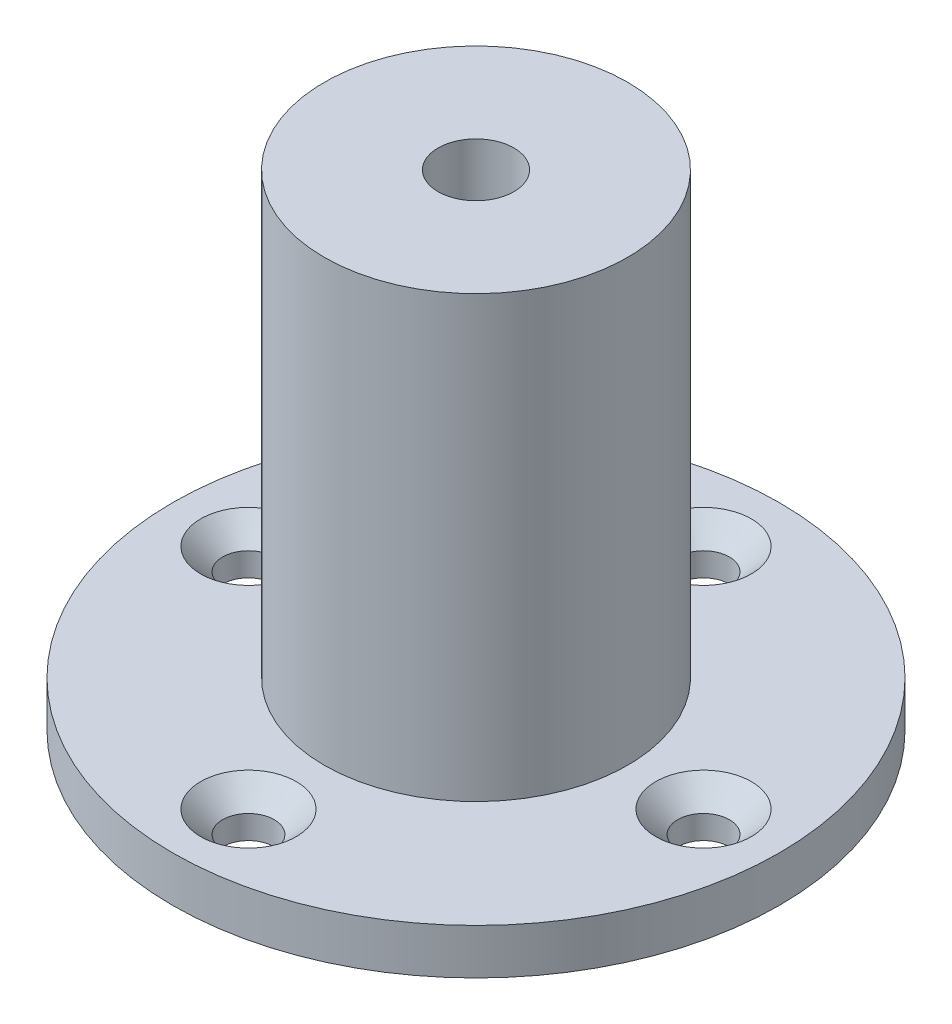
SolidWorks part; units mm, degrees
ref_plane "Front Plane" through (0, 0, 0) normal (0, 0, 1) x (1, 0, 0)
ref_plane "Top Plane" through (0, 0, 0) normal (0, 1, 0) x (1, 0, 0)
ref_plane "Right Plane" through (0, 0, 0) normal (1, 0, 0) x (0, 0, -1)
sketch "Sketch1" plane through (0, 0, 0) normal (0, 1, 0) x (1, 0, 0)
  circle A0 centre (0, 0) radius 10
  dimension "D1" = 20
extrude "Boss-Extrude1" add sketch "Sketch1" along normal blind 32 contours A0
sketch "Sketch2" plane through (0, 0, 0) normal (0, -1, 0) x (1, 0, 0)
  circle A0 centre (0, 0) radius 20
  dimension "D1" = 40
extrude "Boss-Extrude2" add sketch "Sketch2" against normal blind 3
hole_wizard "CSK for M3 Countersunk Flat Head Screw1" positions "Sketch4" profile "Sketch3" countersink size "M3" standard "ISO" end condition through all
sketch "Sketch4" plane through (0, 3, 0) normal (0, 1, 0) x (1, 0, 0)
  point P0 (0, 15)
  dimension "D1" = 15
sketch "Sketch3" plane through (0, 3, -15) normal (1, 0, 0) x (0, 0, 1)
  line L0 (0, 0) -> (0, 3)
  line L1 (0, 3) -> (1.7, 3)
  line L2 (1.7, 3) -> (1.7, 1.45)
  line L3 (1.7, 1.45) -> (3.15, 0)
  line L5 (3.15, 0) -> (0, 0)
  line L6 (-1.7, 1.45) -> (-3.15, 0) construction
  line L11 (0, -6.35) -> (0, 107.95) construction
  dimension "Thru Hole Dia." = 3.4
  dimension "Thru Hole Depth" = 3
  dimension "Near C'Sink Dia." = 6.3
  dimension "Near C'Sink Angle" = 90
pattern_circular "CirPattern1" count 4 over 360 about axis through (0, 3, 0) along (0, -1, 0) of "CSK for M3 Countersunk Flat Head Screw1"
hole_wizard "M6 Tapped Hole1" positions "Sketch6" profile "Sketch5" tap size "M6" standard "ISO"
sketch "Sketch6" plane through (0, 32, 0) normal (0, 1, 0) x (1, 0, 0)
  point P0 (0, 0)
sketch "Sketch5" plane through (0, 32, 0) normal (1, 0, 0) x (0, 0, 1)
  line L0 (0, 0) -> (0, 18.5022)
  line L1 (0, 18.5022) -> (2.5, 17)
  line L2 (2.5, 17) -> (2.5, 0)
  line L5 (2.5, 0) -> (0, 0)
  line L10 (0, 18.5022) -> (-2.5, 17) construction
  line L11 (0, -6.35) -> (0, 107.95) construction
  dimension "Tap Drill Dia." = 5
  dimension "Tap Drill Depth" = 17
  dimension "Drill Angle" = 118
